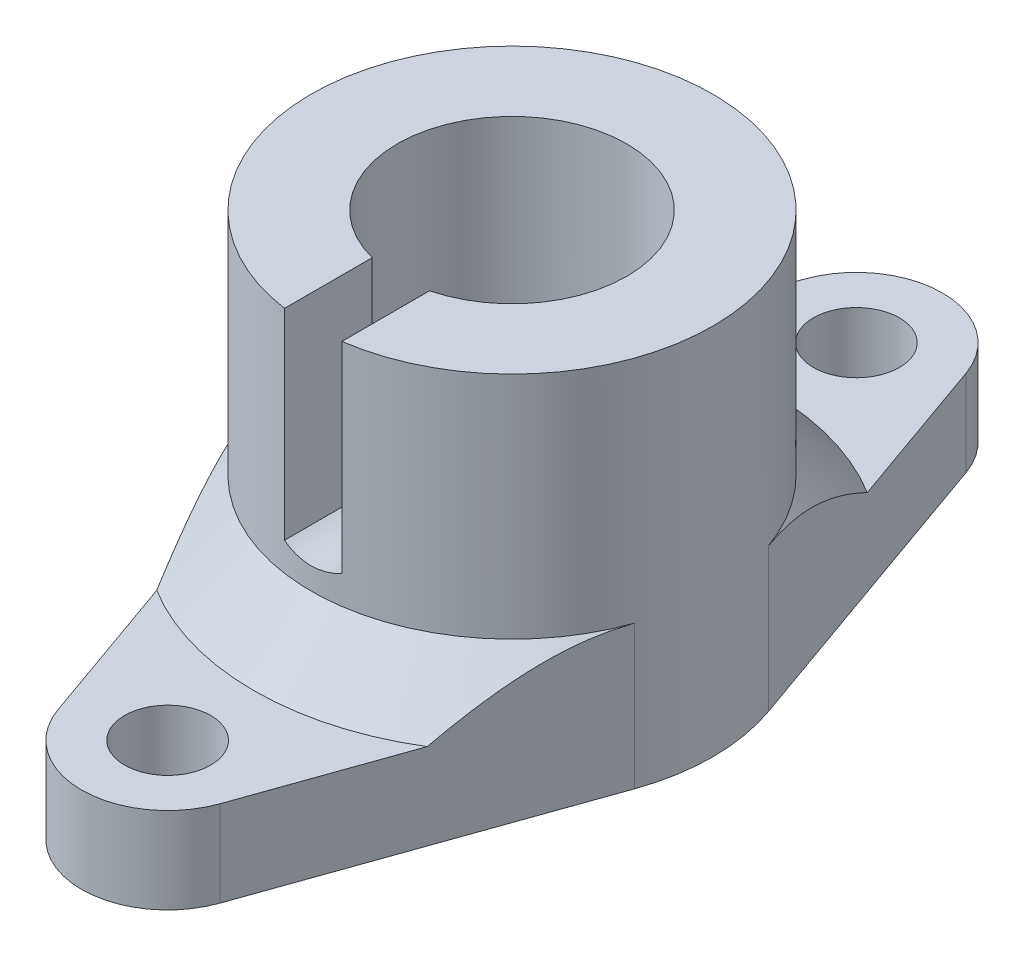
SolidWorks part; units mm, degrees
ref_plane "Alzado" through (0, 0, 0) normal (0, 0, 1) x (1, 0, 0)
ref_plane "Planta" through (0, 0, 0) normal (0, 1, 0) x (1, 0, 0)
ref_plane "Vista lateral" through (0, 0, 0) normal (1, 0, 0) x (0, 0, -1)
sketch "Croquis1" plane through (0, 0, 0) normal (0, 1, 0) x (1, 0, 0)
  circle A0 centre (0, 0) radius 4
  circle A1 centre (0, 0) radius 7
  dimension "D1" = 8
  dimension "D2" = 14
extrude "Saliente-Extruir1" add sketch "Croquis1" along normal blind 10
ref_plane "Plano1" through (0, 0, 10) normal (0, 0, 1) x (1, 0, 0)
sketch "Croquis2" plane through (0, 0, 10) normal (0, 0, 1) x (1, 0, 0)
  line L0 (0, 10) -> (1, 10)
  line L1 (4, 10) -> (-4, 10) construction
  line L2 (1, 10) -> (1, 3)
  line L3 (0, 10) -> (-1, 10)
  line L4 (7, 10) -> (-7, 10) construction
  line L5 (-1, 10) -> (-1, 3)
  line L6 (0, 3) -> (0, 5)
  arc A0 (-1, 3) -> (1.5811, 3.4189) centre (0, 5) ccw
  dimension "D1" = 1
  dimension "D2" = 7
  dimension "D3" = 1
  dimension "D4" = 7
  dimension "D5" = 2
extrude "Cortar-Extruir2" cut sketch "Croquis2" against normal blind 9 and the other way through all
sketch "Croquis3" plane through (0, 0, 0) normal (0, -1, 0) x (1, 0, 0)
  line L0 (0, 0) -> (0, 12)
  line L1 (0, 0) -> (-2.5958, 0) construction
  line L2 (-6.5997, 2.3333) -> (-2.8284, 13)
  line L3 (6.5997, 2.3333) -> (2.8284, 13)
  line L4 (6.5997, -2.3333) -> (2.8284, -13)
  line L5 (-6.5997, -2.3333) -> (-2.8284, -13)
  circle A0 centre (0, 12) radius 1.5
  circle A1 centre (0, 12) radius 3
  circle A2 centre (0, -12) radius 1.5
  circle A3 centre (0, -12) radius 3
  circle A4 centre (0, 0) radius 7 construction
  dimension "D2" = 3
  dimension "D3" = 6
  dimension "D1" = 12
extrude "Saliente-Extruir2" add sketch "Croquis3" along normal blind 3
chamfer "Chaflán1" distance 2 angle 45 2 edges at (0, 0, -7) (0, 0, 7)
